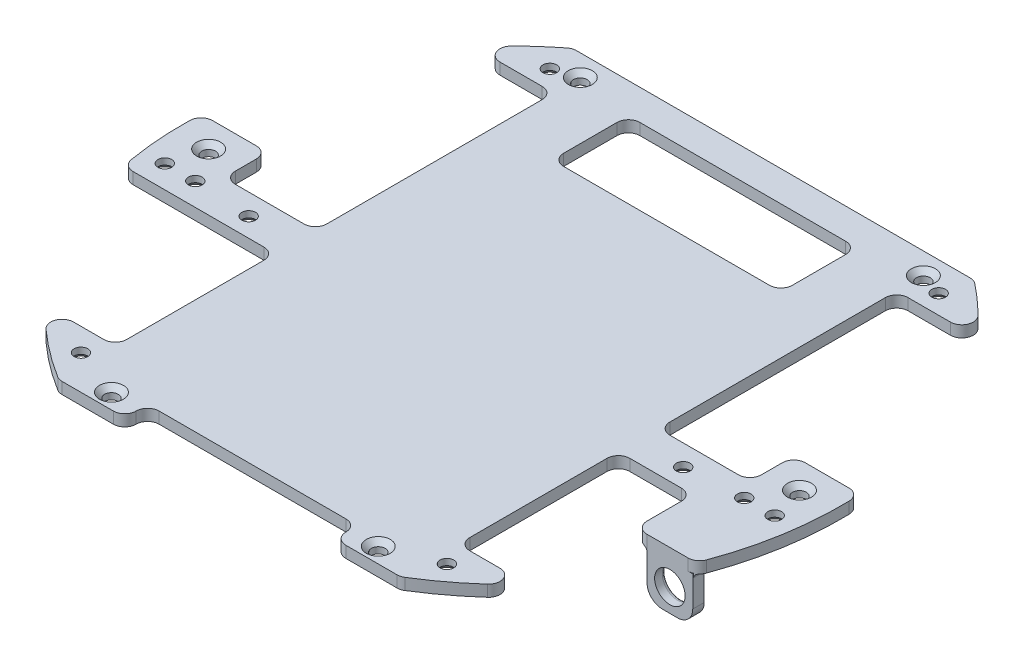
SolidWorks part; units mm, degrees
note: The reader was unsure of these and kept them because the rebuilt part matched: shared geometry of "Sketch21<2>".
material "PET"
ref_plane "Front Plane" through (0, 0, 0) normal (0, 0, 1) x (1, 0, 0)
ref_plane "Top Plane" through (0, 0, 0) normal (0, 1, 0) x (1, 0, 0)
ref_plane "Right Plane" through (0, 0, 0) normal (1, 0, 0) x (0, 0, -1)
sketch "Sketch1" plane through (0, 0, 0) normal (0, 1, 0) x (1, 0, 0)
  line L0 (-52.6579, 68.6251) -> (52.6579, 68.6251)
  line L1 (52.6579, 68.6251) -> (0, 0) construction
  line L2 (0, 0) -> (-52.6579, 68.6251) construction
  arc A0 (-52.6579, 68.6251) -> (52.6579, 68.6251) centre (0, 0) ccw
  arc A1 (52.6579, 68.6251) -> (-52.6579, 68.6251) centre (0, 0) ccw construction
  dimension "D1" = 173
  dimension "D2" = 75
extrude "Boss-Extrude1" add sketch "Sketch1" along normal blind 3
hole_wizard "CSK for M3 Countersunk Flat Head Screw3" positions "Sketch8" profile "Sketch9" countersink size "M3" standard "DIN" end condition through all
sketch "Sketch8" plane through (0, 3, 0) normal (0, -1, 0) x (-1, 0, 0)
  point P0 (45, 63)
  point P2 (-45, 63)
  point P4 (-77.5, -2)
  point P6 (77.5, -2)
  point P8 (35, -70)
  point P10 (-35, -70)
  dimension "D1" = 63
  dimension "D3" = 2
  dimension "D4" = 70
  dimension "D2" = 155
  dimension "D5" = 77.5
  dimension "D6" = 90
  dimension "D7" = 45
  dimension "D8" = 70
  dimension "D9" = 35
sketch "Sketch9" plane through (-45, 3, -63) normal (1, 0, 0) x (0, 0, 1)
  line L0 (0, 0) -> (0, 3)
  line L1 (0, 3) -> (1.8, 3)
  line L2 (1.8, 3) -> (1.8, 1.35)
  line L3 (1.8, 1.35) -> (3.15, 0)
  line L5 (3.15, 0) -> (0, 0)
  line L6 (-1.8, 1.35) -> (-3.15, 0) construction
  line L11 (0, -6.35) -> (0, 107.95) construction
  dimension "Thru Hole Dia." = 3.6
  dimension "Thru Hole Depth" = 3
  dimension "Near C'Sink Dia." = 6.3
  dimension "Near C'Sink Angle" = 90
hole_wizard "CSK for M3 Countersunk Flat Head Screw4" positions "Sketch12" profile "Sketch13" countersink size "M3" standard "DIN" end condition through all
sketch "Sketch12" plane through (0, 0, 0) normal (0, -1, 0) x (-1, 0, 0)
  point P0 (51, 61)
  point P2 (-51, 61)
  point P5 (48, -65)
  point P7 (-48, -65)
  point P16 (80, -11)
  point P20 (-80, -11)
  point P29 (57, -12)
  point P31 (-57, -12)
  point P32 (-72, -11)
  point P35 (72, -11)
  point P38 (0, 0)
  dimension "D1" = 102
  dimension "D2" = 51
  dimension "D3" = 61
  dimension "D4" = 96
  dimension "D6" = 48
  dimension "D5" = 126
  dimension "D12" = 73
  dimension "D14" = 114
  dimension "D13" = 57
  dimension "D7" = 80
  dimension "D8" = 80
  dimension "D9" = 11
  dimension "D10" = 11
  dimension "D11" = 8
  dimension "D15" = 8
sketch "Sketch13" plane through (-51, 0, -61) normal (1, 0, 0) x (0, 0, -1)
  line L0 (0, 0) -> (0, 3)
  line L1 (0, 3) -> (1.8, 3)
  line L2 (1.8, 3) -> (1.8, 1.35)
  line L3 (1.8, 1.35) -> (3.15, 0)
  line L5 (3.15, 0) -> (0, 0)
  line L6 (-1.8, 1.35) -> (-3.15, 0) construction
  line L11 (0, -6.35) -> (0, 107.95) construction
  dimension "Thru Hole Dia." = 3.6
  dimension "Thru Hole Depth" = 3
  dimension "Near C'Sink Dia." = 6.3
  dimension "Near C'Sink Angle" = 90
sketch "Sketch14" plane through (0, 3, 0) normal (0, 1, 0) x (1, 0, 0)
  line L0 (65.9261, 56) -> (45, 56)
  line L1 (45, 56) -> (45, 5)
  line L2 (69, 5) -> (86.3554, 5)
  line L3 (64.5, -17) -> (45, -17)
  line L4 (45, -17) -> (45, -59)
  line L5 (45, -59) -> (63.2554, -59)
  line L6 (0, -1.65) -> (0, 1.65) construction
  line L7 (-45, -59) -> (-63.2554, -59)
  line L8 (-45, -17) -> (-45, -59)
  line L9 (-64.5, -17) -> (-45, -17)
  line L10 (-69, 5) -> (-86.3554, 5)
  line L11 (-45, 56) -> (-45, 5)
  line L12 (-65.9261, 56) -> (-45, 56)
  line L13 (52.6579, 68.6251) -> (-52.6579, 68.6251) construction
  line L14 (-30, 60.6251) -> (30, 60.6251)
  line L15 (-30, 60.6251) -> (-30, 40.6251)
  line L16 (-30, 40.6251) -> (30, 40.6251)
  line L17 (30, 60.6251) -> (30, 40.6251)
  line L21 (39.5, -93) -> (-39.5, -93) construction
  line L22 (-39.5, -93) -> (-39.5, -78) construction
  line L23 (-39.5, -78) -> (39.5, -78) construction
  line L24 (39.5, -78) -> (39.5, -93) construction
  line L26 (44.7912, -74) -> (27.5, -74)
  line L28 (64.5, -17) -> (64.5, -32)
  line L29 (64.5, -32) -> (80.3632, -32)
  line L30 (-64.5, -32) -> (-80.3632, -32) construction
  line L31 (-64.5, -17) -> (-64.5, -32) construction
  line L32 (69.6699, -17) -> (78.3301, -17) construction
  line L33 (64.5, -17) -> (69.6699, -17) construction
  line L34 (78.3301, -17) -> (84.813, -17) construction
  line L35 (-64.5, -17) -> (-84.813, -17)
  line L36 (27.5, -74) -> (27.5, -68)
  line L37 (27.5, -68) -> (-27.5, -68)
  line L38 (-27.5, -68) -> (-27.5, -74)
  line L39 (27.5, -74) -> (-27.5, -74) construction
  line L40 (-27.5, -74) -> (-44.7912, -74)
  line L41 (69, 5) -> (69, -6.5)
  line L42 (69, -6.5) -> (45, -6.5)
  line L43 (45, -6.5) -> (45, 5)
  line L44 (45, 5) -> (69, 5) construction
  line L45 (-69, 5) -> (-69, -6.5)
  line L46 (-69, -6.5) -> (-45, -6.5)
  line L47 (-45, -6.5) -> (-45, 5)
  line L48 (-45, 5) -> (-69, 5) construction
  arc A0 (-52.6579, 68.6251) -> (52.6579, 68.6251) centre (0, 0) ccw construction
  arc A1 (63.2554, -59) -> (80.3632, -32) centre (0, 0) ccw
  arc A2 (86.3554, 5) -> (65.9261, 56) centre (0, 0) ccw
  arc A3 (-86.3554, 5) -> (-65.9261, 56) centre (0, 0) cw
  arc A4 (-63.2554, -59) -> (-80.3632, -32) centre (0, 0) cw
  arc A5 (44.7912, -74) -> (-44.7912, -74) centre (0, 0) cw
  arc A6 (78.3301, -17) -> (69.6699, -17) centre (74, -22.5) ccw construction
  circle A7 centre (-74, -22.5) radius 7 construction
  arc A8 (84.813, -17) -> (80.3632, -32) centre (0, 0) cw construction
  arc A9 (69.6699, -17) -> (78.3301, -17) centre (74, -22.5) ccw construction
  arc A10 (-84.813, -17) -> (-80.3632, -32) centre (0, 0) ccw
  point P29 (0, 68.6251)
  point P30 (0, 60.6251)
  point P38 (0, -78)
  dimension "D15" = 14
  dimension "D1" = 56
  dimension "D2" = 51
  dimension "D3" = 78
  dimension "D4" = 45
  dimension "D5" = 15
  dimension "D6" = 8
  dimension "D7" = 0
  dimension "D8" = 20
  dimension "D9" = 60
  dimension "D10" = 79
  dimension "D11" = 59
  dimension "D12" = 42
  dimension "D13" = 6
  dimension "D14" = 4
  dimension "D16" = 22.5
  dimension "D17" = 9.5
  dimension "D18" = 9.5
  dimension "D19" = 74
  dimension "D20" = 55
  dimension "D21" = 24
  dimension "D22" = 11.5
extrude "Cut-Extrude1" cut sketch "Sketch14" against normal through all
fillet "Fillet1" radius 3 34 edges at (65.9261, 1.5, -56) (45, 1.5, -56) (86.3554, 1.5, -5) (45, 1.5, 17) (45, 1.5, 59) (63.2554, 1.5, 59) (-63.2554, 1.5, 59) (-45, 1.5, 59) (-84.813, 1.5, 17) (-45, 1.5, 17) (-86.3554, 1.5, -5) (-65.9261, 1.5, -56) (-45, 1.5, -56) (-30, 1.5, -40.6251) (-30, 1.5, -60.6251) (30, 1.5, -40.6251) (30, 1.5, -60.6251) (80.3632, 1.5, 32) (64.5, 1.5, 32) (64.5, 1.5, 17) (-52.6579, 1.5, -68.6251) (52.6579, 1.5, -68.6251) (44.7912, 1.5, 74) (-27.5, 1.5, 74) (-27.5, 1.5, 68) (27.5, 1.5, 68) (27.5, 1.5, 74) (-44.7912, 1.5, 74) (-69, 1.5, 6.5) (-69, 1.5, -5) (-45, 1.5, 6.5) (69, 1.5, -5) (69, 1.5, 6.5) (45, 1.5, 6.5)
sketch "Sketch16" plane through (0, 0, 0) normal (0, -1, 0) x (1, 0, 0)
  line L1 (-72.318, 4) -> (-46.318, 4)
  line L2 (-72.318, 4) -> (-72.318, 0)
  line L3 (-72.318, 0) -> (-46.318, 0)
  line L4 (-46.318, 4) -> (-46.318, 0)
  line L6 (-83.476, -5) -> (-72, -5) construction
  point P4 (-72.318, 2)
  point P6 (-46.318, 2)
  dimension "D1" = 4
  dimension "D2" = 26
  dimension "D3" = 10
  dimension "D4" = 7
extrude "Boss-Extrude2" [suppressed] add sketch "Sketch16" along normal blind 12.2
hole_wizard "CSK for M2.5 Countersunk Flat Head Screw1" [suppressed] positions "Sketch17" profile "Sketch18" countersink size "M2.5" standard "DIN"
sketch "Sketch17" [suppressed] plane through (0, 0, 4) normal (0, 0, 1) x (1, 0, 0)
  line L0 (-46.318, -12.2) -> (-72.318, -12.2) construction
  line L1 (-48, 0) -> (-82.318, 0) construction
  point P0 (-69.568, -6.1)
  point P2 (-49.068, -6.1)
  point P8 (-59.318, -12.2)
  dimension "D1" = 20.5
  dimension "D2" = 10.25
  dimension "D3" = 6.1
sketch "Sketch18" plane through (-69.568, -6.1, 4) normal (1, 0, 0) x (0, -1, 0)
  line L0 (0, 0) -> (0, 4)
  line L1 (0, 4) -> (1.55, 4)
  line L2 (1.55, 4) -> (1.55, 1.2)
  line L3 (1.55, 1.2) -> (2.75, 0)
  line L5 (2.75, 0) -> (0, 0)
  line L6 (-1.55, 1.2) -> (-2.75, 0) construction
  line L11 (0, -6.35) -> (0, 107.95) construction
  dimension "Thru Hole Dia." = 3.1
  dimension "Thru Hole Depth" = 4
  dimension "Near C'Sink Dia." = 5.5
  dimension "Near C'Sink Angle" = 90
sketch "Sketch19" [suppressed] plane through (0, 0, 17) normal (0, 0, 1) x (1, 0, 0)
  line L0 (-67.118, -2) -> (-67.118, -10.2)
  line L1 (-67.118, -10.2) -> (-54.768, -10.2)
  line L2 (-67.118, -2) -> (-54.768, -2)
  line L3 (-51.518, -6.95) -> (-51.518, -5.25)
  line L4 (-48, 0) -> (-82.318, 0) construction
  line L5 (-46.318, -12.2) -> (-72.318, -12.2) construction
  arc A1 (-51.518, -5.25) -> (-54.768, -2) centre (-54.768, -5.25) ccw
  arc A2 (-54.768, -10.2) -> (-51.518, -6.95) centre (-54.768, -6.95) ccw
  point P8 (-67.118, -6.1)
  point P14 (-59.318, -12.2)
  dimension "D3" = 6.1
  dimension "D4" = 3.25
  dimension "D1" = 8.2
  dimension "D2" = 15.6
  dimension "D5" = 7.8
extrude "Cut-Extrude2" [suppressed] cut sketch "Sketch19" against normal up to next
chamfer "Chamfer1" [suppressed] distance 3 angle 45
sketch "Sketch21" plane through (0, 0, 0) normal (0, 0, 1) x (1, 0, 0)
  line L1 (67.5, 0) -> (79.5, 0)
  line L2 (67.5, 0) -> (67.5, -12)
  line L3 (67.5, -12) -> (79.5, -12)
  line L4 (79.5, 0) -> (79.5, -12)
  line L5 (67.5, 0) -> (79.5, -12) construction
  line L6 (67.5, -12) -> (79.5, 0) construction
  line L7 (27, 0) -> (30, 0) construction
  circle A0 centre (73.5, -6) radius 4
  point P0 (73.5, -6)
  dimension "D1" = 8
  dimension "D2" = 12
  dimension "D3" = 12
  dimension "D4" = 67.5
extrude "Boss-Extrude3" add sketch "Sketch21" along normal up to surface (32 mm away) up to face at (72.9011, 1.5, 32)
extrude "Cut-Extrude3" cut sketch "Sketch21<2>" along normal offset from surface (29 mm away) 3 contours L2 L1 L4 L3 up to face at (74.0149, -2.5714, 32)
sketch "Sketch21<2>" plane through (0, 0, 0) normal (0, 0, 1) x (1, 0, 0) same geometry as "Sketch21"
fillet "Fillet2" radius 4 2 edges at (79.5, -12, 30.5) (67.5, -12, 30.5)
fillet "Fillet3" radius 1 3 edges at (69.5, -6, 29) (79.5, 0, 30.3753) (67.5, 0, 30.5)
equation "\"D5@Sketch8\"=\"D2@Sketch8\"/2"
equation "\"D7@Sketch8\"=\"D6@Sketch8\"/2"
equation "\"D9@Sketch8\"=\"D8@Sketch8\"/2"
equation "\"D2@Sketch12\"=\"D1@Sketch12\"/2"
equation "\"D6@Sketch12\"=\"D4@Sketch12\"/2"
equation "\"D2@Sketch17\"=\"D1@Sketch17\"/2"
equation "\"D5@Sketch19\"=\"D2@Sketch19\"/2"
equation "\"D13@Sketch12\"=\"D14@Sketch12\"/2"
equation "\"D11@Sketch12\"=\"D15@Sketch12\""
